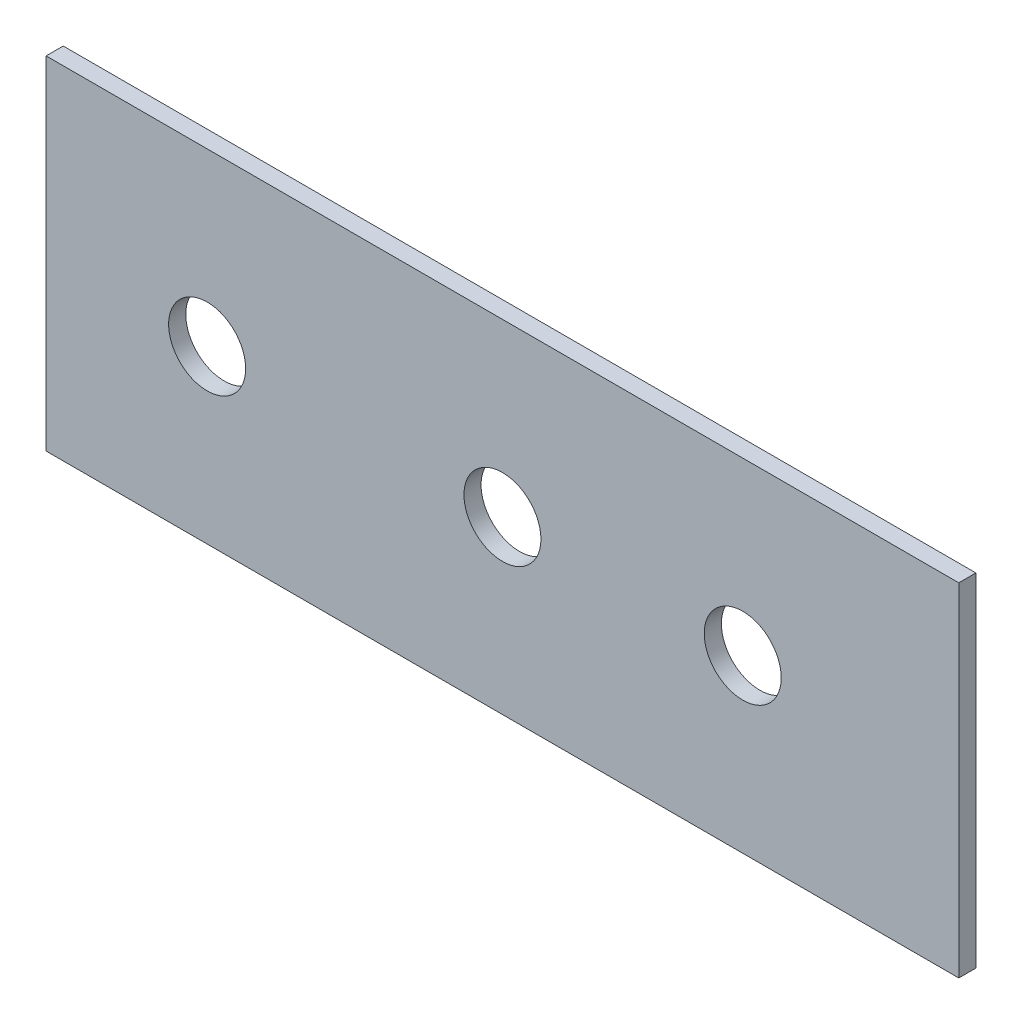
SolidWorks part; units mm, degrees
ref_plane "Plan de face" through (0, 0, 0) normal (0, 0, 1) x (1, 0, 0)
ref_plane "Plan de dessus" through (0, 0, 0) normal (0, 1, 0) x (1, 0, 0)
ref_plane "Plan de droite" through (0, 0, 0) normal (1, 0, 0) x (0, 0, -1)
sketch "Esquisse1" plane through (0, 0, 0) normal (0, 0, 1) x (1, 0, 0)
  line L1 (-160, -60) -> (160, -60)
  line L2 (-160, -60) -> (-160, 60)
  line L3 (-160, 60) -> (160, 60)
  line L4 (160, -60) -> (160, 60)
  line L5 (-160, -60) -> (160, 60) construction
  line L6 (-160, 60) -> (160, -60) construction
  point P0 (0, 0)
  dimension "D1" = 320
  dimension "D2" = 120
extrude "Boss.-Extru.1" add sketch "Esquisse1" along normal blind 6
ref_axis "Axis1" through (-160, 0, 6) along (1, 0, 0)
hole_wizard "M25 Clearance Hole1" positions "Sketch2" profile "Sketch1" hole size "M25" standard "ANSI Metric"
sketch "Sketch2" plane through (0, 0, 6) normal (0, 0, 1) x (1, 0, 0)
  point P0 (-103.5381, 0)
  point P3 (0, 0)
  point P6 (84.254, 0)
sketch "Sketch1" plane through (-103.5381, 0, 6) normal (1, 0, 0) x (0, -1, 0)
  line L0 (0, 0) -> (0, 14.1116)
  line L1 (0, 14.1116) -> (13.5, 6)
  line L2 (13.5, 6) -> (13.5, 0)
  line L5 (13.5, 0) -> (0, 0)
  line L10 (0, 14.1116) -> (-13.5, 6) construction
  line L11 (0, -6.35) -> (0, 107.95) construction
  dimension "Hole Dia." = 27
  dimension "Hole Depth" = 6
  dimension "Drill Angle" = 118
